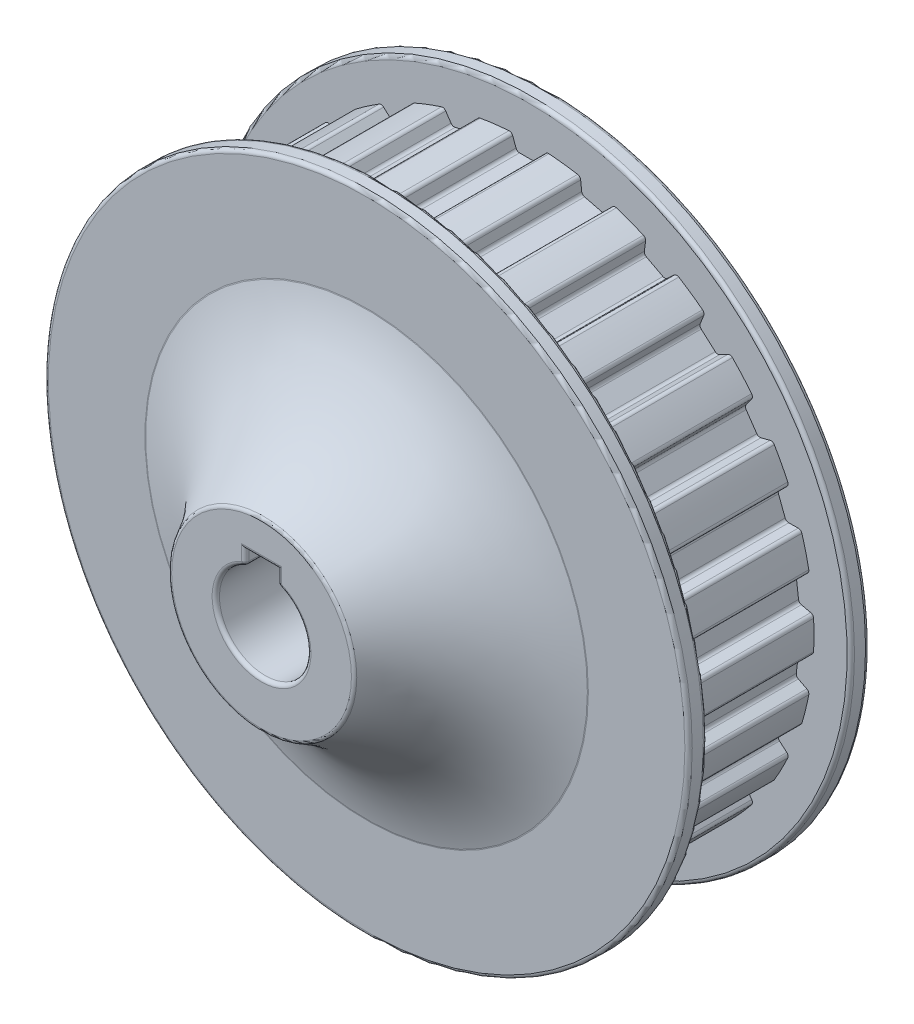
SolidWorks part; units mm, degrees
ref_plane "Front Plane" through (0, 0, 0) normal (0, 0, 1) x (1, 0, 0)
ref_plane "Top Plane" through (0, 0, 0) normal (0, 1, 0) x (1, 0, 0)
ref_plane "Right Plane" through (0, 0, 0) normal (1, 0, 0) x (0, 0, -1)
sketch "Sketch1" plane through (0, 0, 0) normal (0, 1, 0) x (1, 0, 0)
  line L0 (0, 36.1296) -> (0, -19.4741) construction
sketch "Sketch7" plane through (0, 0, 0) normal (0, 0, 1) x (1, 0, 0)
  line L0 (0, 0) -> (0, 37.6222) construction
  line L1 (-2.325, 38.5772) -> (-2.9401, 40.2672) construction
  line L2 (-2.325, 38.5772) -> (-1.6298, 36.6672) construction
  line L3 (-1.6298, 36.6672) -> (1.6298, 36.6672) construction
  line L4 (1.6298, 36.6672) -> (2.325, 38.5772) construction
  line L5 (2.325, 38.5772) -> (-2.325, 38.5772) construction
  line L6 (0, 36.6672) -> (0, 38.5772) construction
  line L7 (2.325, 38.5772) -> (2.9401, 40.2672) construction
  line L8 (-2.9401, 40.2672) -> (2.9401, 40.2672) construction
  line L9 (0, 0) -> (9.0036, 36.529) construction
  line L10 (9.0036, 36.529) -> (9.2489, 37.5242) construction
  line L11 (0, 38.5772) -> (0, 38.6472) construction
  line L12 (0, 38.6472) -> (0, 40.3744) construction
  line L13 (0, 39.5108) -> (9.4556, 38.3627) construction
  line L14 (9.2489, 37.5242) -> (9.6622, 39.2012) construction
  circle A1 centre (0, 0) radius 37.6222 construction
  circle A2 centre (-1.2727, 37.1772) radius 0.51 construction
  circle A3 centre (1.2727, 37.1772) radius 0.51 construction
  circle A4 centre (0, 0) radius 38.6472
  circle A5 centre (0, 0) radius 40.3744 construction
  dimension "D3" = 40
  dimension "D6" = 1.02
  dimension "D1" = 3.6
  dimension "D2" = 13.846
  dimension "D7" = 9.525
  dimension "D4" = 1.91
  dimension "D5" = 4.65
extrude "Boss-Extrude1" add sketch "Sketch7" along normal blind 7.25 and the other way blind 7.25 contours A4 region at (0, 0, 0)
sketch "Sketch14" plane through (0, 0, 0) normal (1, 0, 0) x (0, 0, -1)
  line L0 (-21.5, 0) -> (-21.5, 12.5)
  line L1 (-21.5, 0) -> (0, 0)
  line L2 (0, 0) -> (0, 30)
  line L3 (0, 30) -> (-7.25, 30)
  line L4 (-7.25, 30) -> (-21.5, 12.5)
  line L5 (-7.25, 38.6472) -> (-7.25, -38.6472) construction
  line L6 (-21.5, 8.5407) -> (-4.026, 30) construction
  arc A0 (-7.25, 30) -> (-21.5, 12.5) centre (-33.1527, 36.5404) cw
  point P11 (-7.25, 38)
  dimension "D1" = 12.5
  dimension "D2" = 30
  dimension "D3" = 21.5
  dimension "D4" = 2.5
revolve "Revolve1" add sketch "Sketch14" angle 360 about L0 region at (0, 11.7843, 8.7316) region at (0, 12.7041, 19.1027) region at (0, 27.3191, 7.193)
sketch "Sketch9" plane through (0, 0, 0) normal (0, 0, 1) x (1, 0, 0)
  line L0 (2, 0) -> (-2, 0) construction
  line L1 (-2, 0) -> (-2, 7.5) construction
  line L2 (-2, 7.5) -> (2, 7.5) construction
  line L3 (2, 7.5) -> (2, 0) construction
  circle A0 centre (0, 0) radius 6 construction
  dimension "D1" = 12
  dimension "D2" = 4
  dimension "D3" = 7.5
sketch "Sketch10" plane through (0, 0, 0) normal (0, 0, 1) x (1, 0, 0)
  line L0 (2, 0) -> (-2, 0) construction
  line L1 (-2.2, 7.7) -> (2.2, 7.7)
  line L2 (-2.2, 7.7) -> (-2.2, 0)
  line L3 (-2.2, 0) -> (2.2, 0)
  line L4 (2.2, 7.7) -> (2.2, 0)
  line L5 (-2, 7.5) -> (2, 7.5) construction
  line L6 (2, 7.5) -> (2, 0) construction
  circle A0 centre (0, 0) radius 6.2
  circle A1 centre (0, 0) radius 6 construction
  dimension "D1" = 0.2
  dimension "D2" = 0.2
  dimension "D3" = 0.2
extrude "Cut-Extrude3" cut sketch "Sketch10" against normal through all both and the other way through all contours A0 L4 L1 L2 | L2 A0 L4 L3 | L4 A0 L2 L3 region at (0, 6.8793, 0) region at (0, 3.0348, 0) region at (0, -0.8613, 0)
sketch "Sketch11" plane through (0, 0, 0) normal (0, 1, 0) x (1, 0, 0)
  line L0 (38.6472, 7.25) -> (-38.6472, 7.25) construction
  line L1 (11, 7.25) -> (17.5, 7.25)
  line L2 (11, 7.25) -> (11, 4.75)
  line L3 (11, 4.75) -> (17.5, 4.75)
  line L4 (17.5, 7.25) -> (17.5, 4.75)
  line L5 (-38.6472, -7.25) -> (38.6472, -7.25) construction
  line L6 (11, -7.25) -> (17.5, -7.25)
  line L7 (11, -7.25) -> (11, -4.75)
  line L8 (11, -4.75) -> (17.5, -4.75)
  line L9 (17.5, -7.25) -> (17.5, -4.75)
  line L11 (11, 4.75) -> (11, -4.75) construction
  line L12 (17.5, -4.75) -> (17.5, 4.75) construction
  line L13 (6.2, 7.25) -> (-6.2, 7.25) construction
  line L14 (0, 7.25) -> (22.5, 7.25)
  line L15 (0, 7.25) -> (0, -7.25)
  line L16 (0, -7.25) -> (22.5, -7.25)
  line L17 (22.5, 7.25) -> (22.5, -7.25)
  line L18 (-6.2, -7.25) -> (6.2, -7.25) construction
  line L19 (6, 7.25) -> (6, -7.25) construction
  dimension "D1" = 22.5
  dimension "D2" = 6
  dimension "D3" = 5
  dimension "D4" = 5
  dimension "D5" = 2.5
revolve "Cut-Revolve1" [suppressed] cut sketch "Sketch11" angle 360 about L0
sketch "Sketch15" plane through (0, 0, -7.25) normal (0, 0, -1) x (-1, 0, 0)
  circle A0 centre (0, 0) radius 8.0081
  circle A1 centre (0, 0) radius 2.25
  dimension "D1" = 4.5
extrude "Boss-Extrude2" add sketch "Sketch15" against normal blind 5.5
sketch "Sketch16" plane through (0, 0, -7.25) normal (0, 0, -1) x (-1, 0, 0)
  circle A0 centre (0, 0) radius 5
  dimension "D1" = 10
extrude "Cut-Extrude4" cut sketch "Sketch16" against normal blind 3
sketch "Sketch17" plane through (0, 0, -7.25) normal (0, 0, -1) x (-1, 0, 0)
  circle A0 centre (0, 0) radius 38.6472
  circle A1 centre (0, 0) radius 38.6472 construction
  circle A2 centre (0, 0) radius 5
  circle A3 centre (0, 0) radius 5 construction
extrude "Boss-Extrude3" add sketch "Sketch17" along normal blind 7.5
sketch "Sketch8" plane through (0, 0, 0) normal (0, 0, 1) x (1, 0, 0)
  line L6 (-1.6298, 36.6672) -> (-2.3505, 38.6472)
  line L7 (-2.3505, 38.6472) -> (2.3505, 38.6472)
  line L8 (2.3505, 38.6472) -> (1.6298, 36.6672)
  line L9 (1.6298, 36.6672) -> (-1.6298, 36.6672)
  line L10 (-2.325, 38.5772) -> (-1.6298, 36.6672) construction
  line L11 (1.6298, 36.6672) -> (2.325, 38.5772) construction
  line L12 (7.1926, 35.9918) -> (6.9667, 38.0867)
  line L13 (6.9667, 38.0867) -> (11.5311, 36.9617)
  line L14 (11.5311, 36.9617) -> (10.3575, 35.2117)
  line L15 (10.3575, 35.2117) -> (7.1926, 35.9918)
  line L16 (15.597, 33.2246) -> (15.879, 35.3127)
  line L17 (15.879, 35.3127) -> (20.0415, 33.1281)
  line L18 (20.0415, 33.1281) -> (18.4832, 31.7098)
  line L19 (18.4832, 31.7098) -> (15.597, 33.2246)
  line L20 (23.0949, 28.5266) -> (23.8685, 30.4865)
  line L21 (23.8685, 30.4865) -> (27.3872, 27.3692)
  line L22 (27.3872, 27.3692) -> (25.5348, 26.365)
  line L23 (25.5348, 26.365) -> (23.0949, 28.5266)
  line L24 (29.2507, 22.1707) -> (30.4708, 23.8885)
  line L25 (30.4708, 23.8885) -> (33.1412, 20.0197)
  line L26 (33.1412, 20.0197) -> (31.1024, 19.488)
  line L27 (31.1024, 19.488) -> (29.2507, 22.1707)
  line L28 (33.7065, 14.5263) -> (35.3023, 15.9022)
  line L29 (35.3023, 15.9022) -> (36.9692, 11.5068)
  line L30 (36.9692, 11.5068) -> (34.8624, 11.4785)
  line L31 (34.8624, 11.4785) -> (33.7065, 14.5263)
  line L32 (36.2034, 6.0377) -> (38.0821, 6.9917)
  line L33 (38.0821, 6.9917) -> (38.6487, 2.3251)
  line L34 (38.6487, 2.3251) -> (36.5963, 2.8018)
  line L35 (36.5963, 2.8018) -> (36.2034, 6.0377)
  line L36 (36.5963, -2.8018) -> (38.6487, -2.3251)
  line L37 (38.6487, -2.3251) -> (38.0821, -6.9917)
  line L38 (38.0821, -6.9917) -> (36.2034, -6.0377)
  line L39 (36.2034, -6.0377) -> (36.5963, -2.8018)
  line L40 (34.8624, -11.4785) -> (36.9692, -11.5068)
  line L41 (36.9692, -11.5068) -> (35.3023, -15.9022)
  line L42 (35.3023, -15.9022) -> (33.7065, -14.5263)
  line L43 (33.7065, -14.5263) -> (34.8624, -11.4785)
  line L44 (31.1024, -19.488) -> (33.1412, -20.0197)
  line L45 (33.1412, -20.0197) -> (30.4708, -23.8885)
  line L46 (30.4708, -23.8885) -> (29.2507, -22.1707)
  line L47 (29.2507, -22.1707) -> (31.1024, -19.488)
  line L48 (25.5348, -26.365) -> (27.3872, -27.3692)
  line L49 (27.3872, -27.3692) -> (23.8685, -30.4865)
  line L50 (23.8685, -30.4865) -> (23.0949, -28.5266)
  line L51 (23.0949, -28.5266) -> (25.5348, -26.365)
  line L52 (18.4832, -31.7098) -> (20.0415, -33.1281)
  line L53 (20.0415, -33.1281) -> (15.879, -35.3127)
  line L54 (15.879, -35.3127) -> (15.597, -33.2246)
  line L55 (15.597, -33.2246) -> (18.4832, -31.7098)
  line L56 (10.3575, -35.2117) -> (11.5311, -36.9617)
  line L57 (11.5311, -36.9617) -> (6.9667, -38.0867)
  line L58 (6.9667, -38.0867) -> (7.1926, -35.9918)
  line L59 (7.1926, -35.9918) -> (10.3575, -35.2117)
  line L60 (1.6298, -36.6672) -> (2.3505, -38.6472)
  line L61 (2.3505, -38.6472) -> (-2.3505, -38.6472)
  line L62 (-2.3505, -38.6472) -> (-1.6298, -36.6672)
  line L63 (-1.6298, -36.6672) -> (1.6298, -36.6672)
  line L64 (-7.1926, -35.9918) -> (-6.9667, -38.0867)
  line L65 (-6.9667, -38.0867) -> (-11.5311, -36.9617)
  line L66 (-11.5311, -36.9617) -> (-10.3575, -35.2117)
  line L67 (-10.3575, -35.2117) -> (-7.1926, -35.9918)
  line L68 (-15.597, -33.2246) -> (-15.879, -35.3127)
  line L69 (-15.879, -35.3127) -> (-20.0415, -33.1281)
  line L70 (-20.0415, -33.1281) -> (-18.4832, -31.7098)
  line L71 (-18.4832, -31.7098) -> (-15.597, -33.2246)
  line L72 (-23.0949, -28.5266) -> (-23.8685, -30.4865)
  line L73 (-23.8685, -30.4865) -> (-27.3872, -27.3692)
  line L74 (-27.3872, -27.3692) -> (-25.5348, -26.365)
  line L75 (-25.5348, -26.365) -> (-23.0949, -28.5266)
  line L76 (-29.2507, -22.1707) -> (-30.4708, -23.8885)
  line L77 (-30.4708, -23.8885) -> (-33.1412, -20.0197)
  line L78 (-33.1412, -20.0197) -> (-31.1024, -19.488)
  line L79 (-31.1024, -19.488) -> (-29.2507, -22.1707)
  line L80 (-33.7065, -14.5263) -> (-35.3023, -15.9022)
  line L81 (-35.3023, -15.9022) -> (-36.9692, -11.5068)
  line L82 (-36.9692, -11.5068) -> (-34.8624, -11.4785)
  line L83 (-34.8624, -11.4785) -> (-33.7065, -14.5263)
  line L84 (-36.2034, -6.0377) -> (-38.0821, -6.9917)
  line L85 (-38.0821, -6.9917) -> (-38.6487, -2.3251)
  line L86 (-38.6487, -2.3251) -> (-36.5963, -2.8018)
  line L87 (-36.5963, -2.8018) -> (-36.2034, -6.0377)
  line L88 (-36.5963, 2.8018) -> (-38.6487, 2.3251)
  line L89 (-38.6487, 2.3251) -> (-38.0821, 6.9917)
  line L90 (-38.0821, 6.9917) -> (-36.2034, 6.0377)
  line L91 (-36.2034, 6.0377) -> (-36.5963, 2.8018)
  line L92 (-34.8624, 11.4785) -> (-36.9692, 11.5068)
  line L93 (-36.9692, 11.5068) -> (-35.3023, 15.9022)
  line L94 (-35.3023, 15.9022) -> (-33.7065, 14.5263)
  line L95 (-33.7065, 14.5263) -> (-34.8624, 11.4785)
  line L96 (-31.1024, 19.488) -> (-33.1412, 20.0197)
  line L97 (-33.1412, 20.0197) -> (-30.4708, 23.8885)
  line L98 (-30.4708, 23.8885) -> (-29.2507, 22.1707)
  line L99 (-29.2507, 22.1707) -> (-31.1024, 19.488)
  line L100 (-25.5348, 26.365) -> (-27.3872, 27.3692)
  line L101 (-27.3872, 27.3692) -> (-23.8685, 30.4865)
  line L102 (-23.8685, 30.4865) -> (-23.0949, 28.5266)
  line L103 (-23.0949, 28.5266) -> (-25.5348, 26.365)
  line L104 (-18.4832, 31.7098) -> (-20.0415, 33.1281)
  line L105 (-20.0415, 33.1281) -> (-15.879, 35.3127)
  line L106 (-15.879, 35.3127) -> (-15.597, 33.2246)
  line L107 (-15.597, 33.2246) -> (-18.4832, 31.7098)
  line L108 (-10.3575, 35.2117) -> (-11.5311, 36.9617)
  line L109 (-11.5311, 36.9617) -> (-6.9667, 38.0867)
  line L110 (-6.9667, 38.0867) -> (-7.1926, 35.9918)
  line L111 (-7.1926, 35.9918) -> (-10.3575, 35.2117)
  circle A0 centre (0, 0) radius 38.6472 construction
  point P119 (0, 0)
  dimension "D1" = 26
extrude "Cut-Extrude2" cut sketch "Sketch8" against normal through all both and the other way through all
fillet "Fillet2" radius 0.51 104 edges at (-11.4896, -36.8998, -3.75) (-6.9747, -38.0126, -3.75) (-2.325, -38.5772, -3.75) (2.325, -38.5772, -3.75) (6.9747, -38.0126, -3.75) (11.4896, -36.8998, -3.75) (15.869, -35.2389, -3.75) (19.9864, -33.0779, -3.75) (23.8411, -30.4172, -3.75) (27.3217, -27.3337, -3.75) (30.4277, -23.8278, -3.75) (33.0692, -20.0009, -3.75) (35.2459, -15.8536, -3.75) (36.8948, -11.5058, -3.75) (38.0157, -6.958, -3.75) (38.5762, -2.3419, -3.75) (38.5762, 2.3419, -3.75) (38.0157, 6.958, -3.75) (36.8948, 11.5058, -3.75) (35.2459, 15.8536, -3.75) (33.0692, 20.0009, -3.75) (30.4277, 23.8278, -3.75) (27.3217, 27.3337, -3.75) (23.8411, 30.4172, -3.75) (19.9864, 33.0779, -3.75) (15.869, 35.2389, -3.75) (11.4896, 36.8998, -3.75) (6.9747, 38.0126, -3.75) (2.325, 38.5772, -3.75) (-10.3575, -35.2117, -3.75) (-7.1926, -35.9918, -3.75) (-1.6298, -36.6672, -3.75) (1.6298, -36.6672, -3.75) (7.1926, -35.9918, -3.75) (10.3575, -35.2117, -3.75) (15.597, -33.2246, -3.75) (18.4832, -31.7098, -3.75) (23.0949, -28.5266, -3.75) (25.5348, -26.365, -3.75) (29.2507, -22.1707, -3.75) (31.1024, -19.488, -3.75) (33.7065, -14.5263, -3.75) (34.8624, -11.4785, -3.75) (36.2034, -6.0377, -3.75) (36.5963, -2.8018, -3.75) (36.5963, 2.8018, -3.75) (36.2034, 6.0377, -3.75) (34.8624, 11.4785, -3.75) (33.7065, 14.5263, -3.75) (31.1024, 19.488, -3.75) (29.2507, 22.1707, -3.75) (25.5348, 26.365, -3.75) (23.0949, 28.5266, -3.75) (18.4832, 31.7098, -3.75) (15.597, 33.2246, -3.75) (10.3575, 35.2117, -3.75) (7.1926, 35.9918, -3.75) (1.6298, 36.6672, -3.75) (-1.6298, 36.6672, -3.75) (-2.325, 38.5772, -3.75) (-15.869, -35.2389, -3.75) (-15.597, -33.2246, -3.75) (-18.4832, -31.7098, -3.75) (-19.9864, -33.0779, -3.75) (-23.8411, -30.4172, -3.75) (-23.0949, -28.5266, -3.75) (-25.5348, -26.365, -3.75) (-27.3217, -27.3337, -3.75) (-30.4277, -23.8278, -3.75) (-29.2507, -22.1707, -3.75) (-31.1024, -19.488, -3.75) (-33.0692, -20.0009, -3.75) (-35.2459, -15.8536, -3.75) (-33.7065, -14.5263, -3.75) (-34.8624, -11.4785, -3.75) (-36.8948, -11.5058, -3.75) (-38.0157, -6.958, -3.75) (-36.2034, -6.0377, -3.75) (-36.5963, -2.8018, -3.75) (-38.5762, -2.3419, -3.75) (-38.5762, 2.3419, -3.75) (-36.5963, 2.8018, -3.75) (-36.2034, 6.0377, -3.75) (-36.8948, 11.5058, -3.75) (-34.8624, 11.4785, -3.75) (-33.7065, 14.5263, -3.75) (-35.2459, 15.8536, -3.75) (-33.0692, 20.0009, -3.75) (-31.1024, 19.488, -3.75) (-29.2507, 22.1707, -3.75) (-30.4277, 23.8278, -3.75) (-27.3217, 27.3337, -3.75) (-25.5348, 26.365, -3.75) (-23.0949, 28.5266, -3.75) (-23.8411, 30.4172, -3.75) (-19.9864, 33.0779, -3.75) (-18.4832, 31.7098, -3.75) (-15.597, 33.2246, -3.75) (-15.869, 35.2389, -3.75) (-11.4896, 36.8998, -3.75) (-10.3575, 35.2117, -3.75) (-7.1926, 35.9918, -3.75) (-6.9747, 38.0126, -3.75) (-38.0157, 6.958, -3.75)
sketch "Sketch18" plane through (0, 0, -14.75) normal (0, 0, -1) x (-1, 0, 0)
  circle A0 centre (0, 0) radius 5
  circle A1 centre (0, 0) radius 43.6472
  circle A2 centre (0, 0) radius 38.6472
  circle A3 centre (0, 0) radius 5 construction
  arc A4 (-2.7092, 38.5521) -> (-6.5957, 38.0802) centre (0, 0) ccw construction
  dimension "D1" = 5
extrude "Boss-Extrude4" add sketch "Sketch18" along normal blind 2.5 contours A1 A2 | A2 A0 region at (42.4127, 0, -14.75) region at (37.5541, 0, -14.75)
sketch "Sketch19" plane through (0, 0, 7.25) normal (0, 0, 1) x (1, 0, 0)
  circle A0 centre (0, 0) radius 30
  circle A1 centre (0, 0) radius 43.6472
  circle A2 centre (0, 0) radius 43.6472 construction
  circle A3 centre (0, 0) radius 30 construction
extrude "Boss-Extrude5" add sketch "Sketch19" against normal blind 2.5
fillet "Fillet3" radius 0.5 19 edges at (2.2, 5.7966, 9.875) (-2.2, 5.7966, 9.875) (2.2, 6.7483, 21.5) (-2.2, 6.7483, 21.5) (0, 7.7, 21.5) (-30, 0, 7.25) (-12.5, 0, 21.5) (0, -6.2, 21.5) (-5, 0, -4.25) (-2.25, 0, -4.25) (-2.2, 6.7483, -1.75) (2.2, 6.7483, -1.75) (43.6472, 0, 4.75) (-43.6472, 0, -14.75) (-43.6472, 0, -17.25) (43.6472, 0, 7.25) (0, 7.7, -1.75) (0, -6.2, -1.75) (-5, 0, -17.25)
